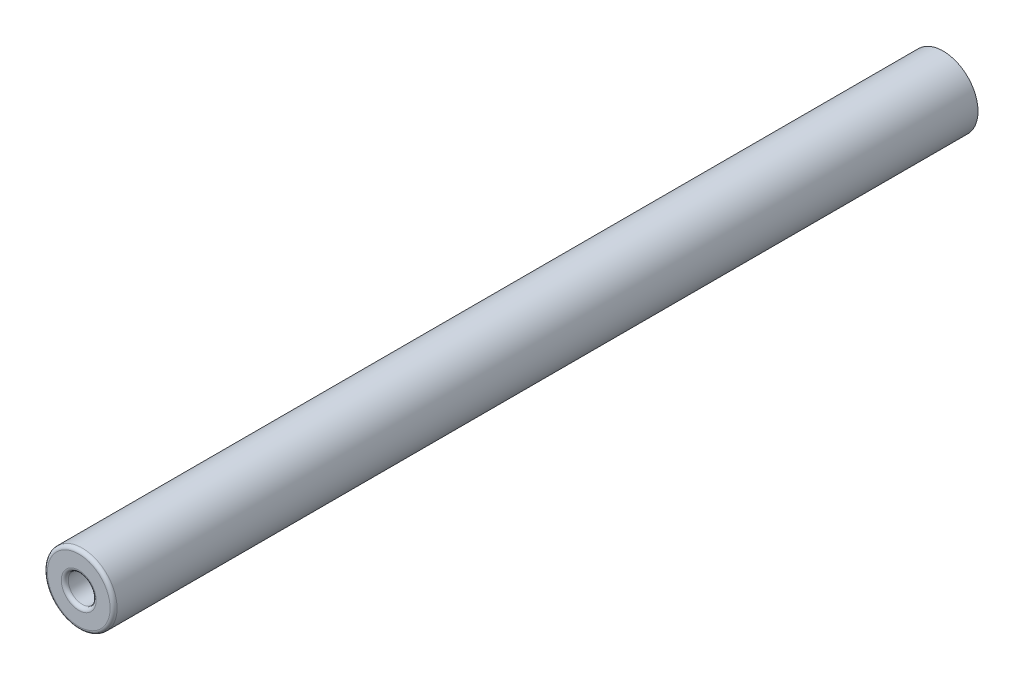
SolidWorks part; units mm, degrees
material "Acero aleado"
ref_plane "Alzado" through (0, 0, 0) normal (0, 0, 1) x (1, 0, 0)
ref_plane "Planta" through (0, 0, 0) normal (0, 1, 0) x (1, 0, 0)
ref_plane "Vista lateral" through (0, 0, 0) normal (1, 0, 0) x (0, 0, -1)
sketch "Croquis1" plane through (0, 0, 0) normal (0, 0, 1) x (1, 0, 0)
  circle A0 centre (0, 0) radius 2.5
  dimension "D1" = 5
extrude "Saliente-Extruir1" add sketch "Croquis1" along normal blind 62
sketch "Croquis2" plane through (0, 0, 62) normal (0, 0, 1) x (1, 0, 0)
  circle A0 centre (0, 0) radius 1
  dimension "D1" = 2
extrude "Cortar-Extruir1" cut sketch "Croquis2" against normal blind 10
fillet "Redondeo1" radius 0.25 2 edges at (2.5, 0, 62) (1, 0, 62)
